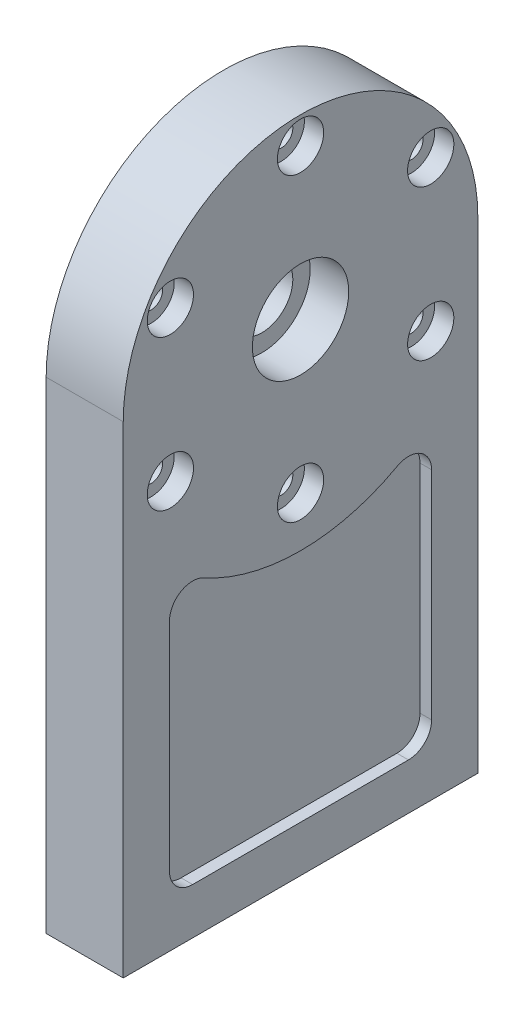
SolidWorks part; units mm, degrees
ref_plane "Front Plane" through (0, 0, 0) normal (0, 0, 1) x (1, 0, 0)
ref_plane "Top Plane" through (0, 0, 0) normal (0, 1, 0) x (1, 0, 0)
ref_plane "Right Plane" through (0, 0, 0) normal (1, 0, 0) x (0, 0, -1)
sketch "Sketch1" plane through (0, 0, 0) normal (1, 0, 0) x (0, 0, -1)
  line L0 (0, 125) -> (0, 0) construction
  line L1 (46, 125) -> (46, 0)
  line L2 (-46, 125) -> (-46, 0)
  line L3 (-46, 0) -> (46, 0)
  arc A0 (46, 125) -> (-46, 125) centre (0, 125) ccw
  point P3 (0, 42.9729)
  dimension "D1" = 46
  dimension "D2" = 125
  dimension "D3" = 92
extrude "Boss-Extrude1" add sketch "Sketch1" along normal mid plane 20 contours A0 L2 L3 L1
sketch "Sketch2" plane through (10, 0, 0) normal (1, 0, 0) x (0, 0, -1)
  line L1 (-46, 125) -> (-46, 0) construction
  line L4 (-34, 74.2063) -> (-34, 18)
  line L6 (34, 74.2063) -> (34, 18)
  line L7 (-28, 12) -> (28, 12)
  line L8 (-46, 0) -> (46, 0) construction
  line L9 (46, 125) -> (46, 0) construction
  arc A0 (-25.1034, 79.4608) -> (25.1034, 79.4608) centre (0, 125) ccw
  arc A1 (-34, 18) -> (-28, 12) centre (-28, 18) ccw
  arc A2 (34, 18) -> (28, 12) centre (28, 18) cw
  arc A3 (-25.1034, 79.4608) -> (-34, 74.2063) centre (-28, 74.2063) ccw
  arc A4 (25.1034, 79.4608) -> (34, 74.2063) centre (28, 74.2063) cw
  point P18 (-34, 85.6554)
  dimension "D1" = 104
  dimension "D5" = 6
  dimension "D2" = 12
  dimension "D3" = 12
  dimension "D4" = 12
extrude "Cut-Extrude1" cut sketch "Sketch2" against normal blind 3
mirror "Mirror1" about plane through (0, 0, 0) normal (1, 0, 0) of "Cut-Extrude1"
sketch "Sketch3" plane through (10, 0, 0) normal (1, 0, 0) x (0, 0, -1)
  circle A0 centre (0, 125) radius 39 construction
  circle A1 centre (0, 164) radius 6
  circle A2 centre (0, 164) radius 3
  dimension "D1" = 78
  dimension "D2" = 12
  dimension "D3" = 6
extrude "Cut-Extrude2" cut sketch "Sketch3" against normal blind 5 contours A1
extrude "Cut-Extrude3" cut sketch "Sketch3<3>" against normal through all contours A2 region at (10, 164, 0)
sketch "Sketch3<3>" plane through (10, 0, 0) normal (1, 0, 0) x (0, 0, -1) same geometry as "Sketch3"
pattern_circular "CirPattern1" count 6 over 360 about axis through (10, 125, 0) along (1, 0, 0) of "Cut-Extrude3", "Cut-Extrude2"
sketch "Sketch4" plane through (10, 0, 0) normal (1, 0, 0) x (0, 0, -1)
  circle A0 centre (0, 125) radius 12.5
  circle A1 centre (0, 125) radius 8
  dimension "D1" = 25
  dimension "D2" = 16
extrude "Cut-Extrude4" cut sketch "Sketch4" against normal blind 10 contours A0
extrude "Cut-Extrude5" cut sketch "Sketch4<3>" against normal through all contours A1 region at (10, 125, 0)
sketch "Sketch4<3>" plane through (10, 0, 0) normal (1, 0, 0) x (0, 0, -1) same geometry as "Sketch4"
sketch "Sketch5" plane through (0, 0, 0) normal (0, -1, 0) x (1, 0, 0)
  circle A0 centre (0, 30) radius 5
  circle A1 centre (0, -30) radius 5
  dimension "D1" = 10
  dimension "D3" = 30
  dimension "D4" = 30
extrude "Cut-Extrude6" cut sketch "Sketch5" against normal blind 15
